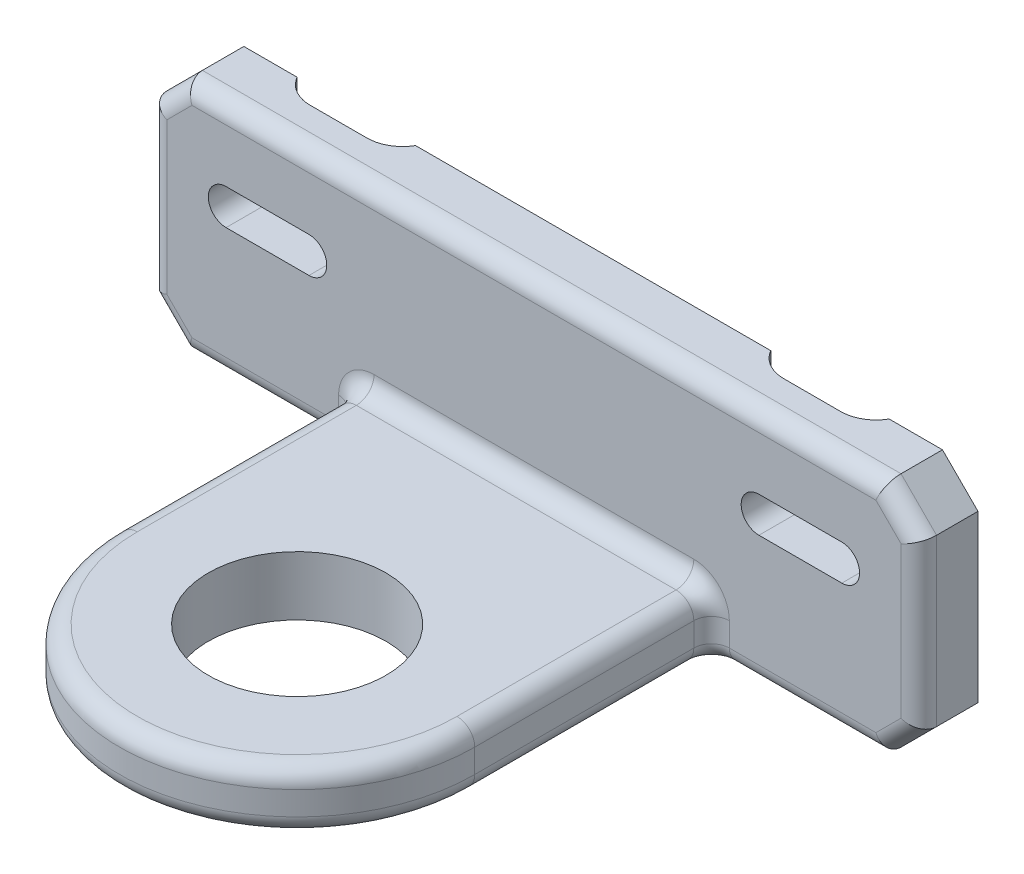
SolidWorks part; units mm, degrees
ref_plane "Plan de face" through (0, 0, 0) normal (0, 0, 1) x (1, 0, 0)
ref_plane "Plan de dessus" through (0, 0, 0) normal (0, 1, 0) x (1, 0, 0)
ref_plane "Plan de droite" through (0, 0, 0) normal (1, 0, 0) x (0, 0, -1)
sketch "Esquisse1" plane through (0, 0, 0) normal (0, 0, 1) x (1, 0, 0)
  line L1 (-65, -20) -> (65, -20)
  line L2 (-65, -20) -> (-65, 20)
  line L3 (-65, 20) -> (65, 20)
  line L4 (65, -20) -> (65, 20)
  line L5 (-65, -20) -> (65, 20) construction
  line L6 (-65, 20) -> (65, -20) construction
  point P0 (0, 0)
  dimension "D1" = 130
  dimension "D2" = 40
extrude "Boss.-Extru.1" add sketch "Esquisse1" along normal blind 10 contours L3 L4 L1 L2
sketch "Esquisse2" plane through (0, -20, 0) normal (0, -1, 0) x (1, 0, 0)
  line L0 (-30, 0) -> (-30, 50)
  line L1 (-65, 0) -> (65, 0) construction
  line L2 (30, 50) -> (30, 0)
  line L3 (30, 0) -> (-30, 0)
  arc A0 (-30, 50) -> (30, 50) centre (0, 50) cw
  circle A1 centre (0, 50) radius 15
  point P6 (0, 0)
  dimension "D1" = 30
  dimension "D3" = 30
  dimension "D2" = 50
extrude "Boss.-Extru.2" add sketch "Esquisse2" against normal blind 10
sketch "Esquisse3" plane through (0, 0, 10) normal (0, 0, 1) x (1, 0, 0)
  line L0 (38, 5) -> (52, 5) construction
  line L1 (38, 8) -> (52, 8)
  line L2 (38, 2) -> (52, 2)
  line L3 (65, -20) -> (65, 20) construction
  line L4 (-65, 20) -> (65, 20) construction
  arc A0 (38, 8) -> (38, 2) centre (38, 5) ccw
  arc A1 (52, 2) -> (52, 8) centre (52, 5) ccw
  point P2 (45, 5)
  point P11 (35, 5)
  point P12 (55, 5)
  point P13 (45, 2)
  dimension "D1" = 20
  dimension "D2" = 15
  dimension "D3" = 20
  dimension "D4" = 6
extrude "Enlèv. mat.-Extru.1" cut sketch "Esquisse3" against normal through all
mirror "Symétrie1" about plane through (0, 0, 0) normal (1, 0, 0) of "Enlèv. mat.-Extru.1"
sketch "Esquisse4" plane through (0, -20, 0) normal (0, -1, 0) x (1, 0, 0)
  line L0 (-65, 0) -> (65, 0) construction
  line L1 (30, 0) -> (50, 0)
  line L2 (30, 0) -> (30, 3)
  line L3 (30, 3) -> (50, 3)
  line L4 (50, 0) -> (50, 3)
  line L5 (0, 35) -> (0, 0) construction
  circle A0 centre (0, 50) radius 15 construction
  point P11 (0, 0)
  point P12 (0, 0)
  dimension "D1" = 20
  dimension "D2" = 3
extrude "Enlèv. mat.-Extru.2" cut sketch "Esquisse4" against normal through all contours L3 L4 L1 L2
fillet "Congé1" radius 6 3 edges at (50, -9, 3) (50, 14, 3) (30, 0, 3)
mirror "Symétrie2" about plane through (0, 0, 0) normal (1, 0, 0) of "Congé1", "Enlèv. mat.-Extru.2"
chamfer "Chanfrein1" distance 6 angle 45 4 edges at (-65, 20, 5) (65, 20, 5) (65, -20, 5) (-65, -20, 5)
fillet "Congé2" radius 3 18 edges at (30, -20, 30) (30, -15, 10) (0, -20, 80) (0, -10, 10) (-30, -20, 30) (30, -10, 30) (-30, -10, 30) (0, -10, 80) (44.5, -20, 10) (65, 0, 10) (62, 17, 10) (62, -17, 10) (0, 20, 10) (-62, 17, 10) (-65, 0, 10) (-62, -17, 10) (-44.5, -20, 10) (-30, -15, 10)
